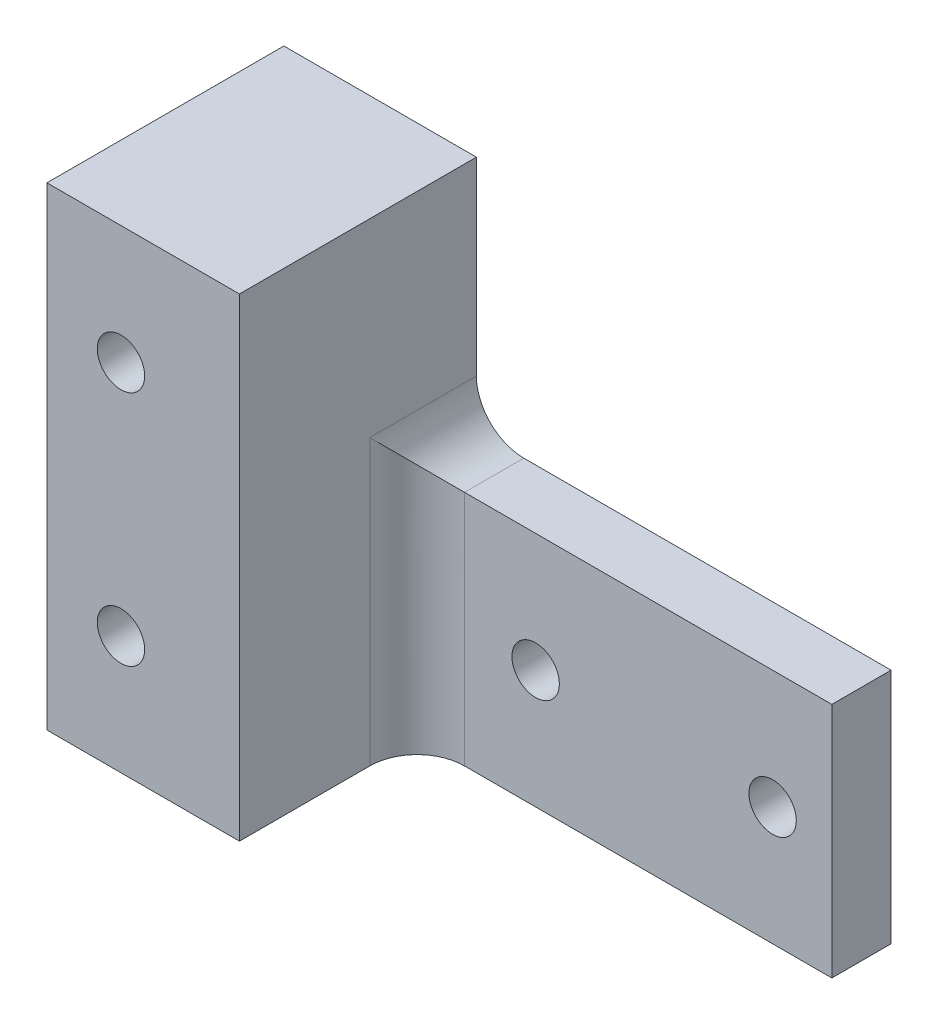
SolidWorks part; units mm, degrees
ref_plane "Front Plane" through (0, 0, 0) normal (0, 0, 1) x (1, 0, 0)
ref_plane "Top Plane" through (0, 0, 0) normal (0, 1, 0) x (1, 0, 0)
ref_plane "Right Plane" through (0, 0, 0) normal (1, 0, 0) x (0, 0, -1)
sketch "Sketch1" plane through (0, 0, 0) normal (0, 0, 1) x (1, 0, 0)
  line L0 (0, 0) -> (0, 50.8)
  line L1 (0, 50.8) -> (25.4, 50.8)
  line L2 (25.4, 50.8) -> (25.4, 25.4)
  line L3 (25.4, 25.4) -> (69.85, 25.4)
  line L4 (69.85, 25.4) -> (69.85, 0)
  line L5 (69.85, 0) -> (0, 0)
  dimension "D1" = 50.8
  dimension "D2" = 25.4
  dimension "3" = 69.85
extrude "Boss-Extrude1" add sketch "Sketch1" along normal blind 25.4
sketch "Sketch2" plane through (0, 0, 25.4) normal (0, 0, 1) x (1, 0, 0)
  line L0 (25.4, 50.8) -> (0, 50.8) construction
  line L1 (25.4, 25.4) -> (25.4, 50.8) construction
  line L2 (0, 0) -> (69.85, 0) construction
  circle A0 centre (12.7, 38.1) radius 2.54
  circle A1 centre (12.7, 12.7) radius 2.54
  circle A2 centre (38.1, 12.7) radius 2.54
  circle A3 centre (63.5, 12.7) radius 2.54
  dimension "D1" = 5.08
  dimension "D2" = 12.7
  dimension "D3" = 12.7
  dimension "D4" = 12.7
  dimension "D5" = 3
extrude "Cut-Extrude1" cut sketch "Sketch2" against normal through all
sketch "Sketch3" plane through (0, 0, 25.4) normal (0, 0, 1) x (1, 0, 0)
  line L0 (25.4, 50.8) -> (0, 50.8) construction
  line L1 (0, 0) -> (4.7625, 0)
  line L2 (0, 0) -> (0, 50.8)
  line L3 (0, 50.8) -> (4.7625, 50.8)
  line L4 (4.7625, 0) -> (4.7625, 50.8)
  dimension "D1" = 4.7625
extrude "Cut-Extrude2" cut sketch "Sketch3" against normal through all
sketch "Sketch4" plane through (0, 0, 0) normal (0, -1, 0) x (1, 0, 0)
  line L5 (69.85, 25.4) -> (25.4, 25.4)
  line L6 (69.85, 25.4) -> (69.85, 6.35)
  line L7 (69.85, 6.35) -> (25.4, 6.35)
  line L8 (25.4, 25.4) -> (25.4, 6.35)
  dimension "D1" = 19.05
  dimension "D2" = 44.45
extrude "Cut-Extrude3" cut sketch "Sketch4" against normal through all
fillet "Fillet1" radius 5.08 2 edges at (25.4, 25.4, 3.175) (25.4, 12.7, 6.35)
sketch "Sketch6" plane through (0, 0, 0) normal (0, 0, -1) x (-1, 0, 0)
  circle A0 centre (-12.7, 38.1) radius 4.445
  dimension "D1" = 8.89
extrude "Cut-Extrude5" cut sketch "Sketch6" against normal blind 12.7
